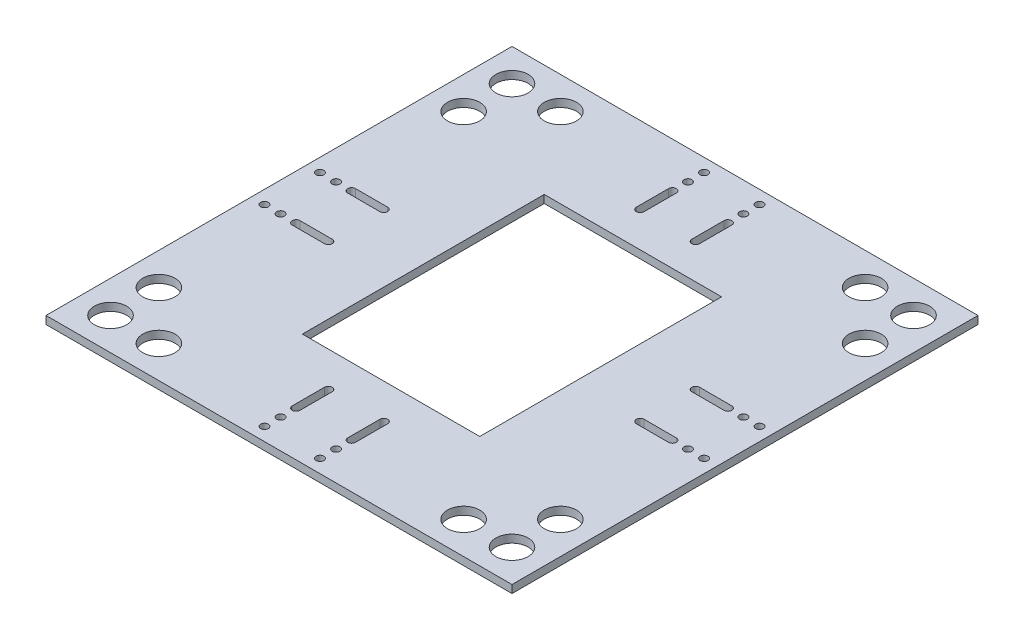
SolidWorks part; units mm, degrees
material "Acrylic (Medium-high impact)"
ref_plane "Front Plane" through (0, 0, 0) normal (0, 0, 1) x (1, 0, 0)
ref_plane "Top Plane" through (0, 0, 0) normal (0, 1, 0) x (1, 0, 0)
ref_plane "Right Plane" through (0, 0, 0) normal (1, 0, 0) x (0, 0, -1)
sketch "Sketch3" plane through (0, 0, 0) normal (0, 1, 0) x (1, 0, 0)
  line L1 (0, 0) -> (183.52, 0)
  line L2 (0, 0) -> (0, 183.52)
  line L3 (0, 183.52) -> (183.52, 183.52)
  line L4 (183.52, 0) -> (183.52, 183.52)
  dimension "D1" = 183.52
  dimension "D2" = 183.52
extrude "Boss-Extrude1" add sketch "Sketch3" along normal blind 3.0988
sketch "Sketch4" plane through (0, 3.0988, 0) normal (0, 1, 0) x (1, 0, 0)
  line L0 (0, 91.76) -> (183.52, 91.76) construction
  line L1 (0, 183.52) -> (0, 0) construction
  line L2 (183.52, 0) -> (183.52, 183.52) construction
  line L3 (91.76, 183.52) -> (91.76, 0) construction
  line L4 (-1025.7031, 102.682) -> (48974.2969, 102.682) construction
  line L5 (17.646, 101.158) -> (30.346, 101.158)
  line L6 (17.646, 104.206) -> (30.346, 104.206)
  line L7 (183.52, 183.52) -> (0, 183.52) construction
  line L8 (0, 0) -> (183.52, 0) construction
  line L9 (-1025.7031, 80.838) -> (48974.2969, 80.838) construction
  line L10 (17.646, 79.314) -> (30.346, 79.314)
  line L11 (17.646, 82.362) -> (30.346, 82.362)
  line L12 (1240.6011, 80.838) -> (-48759.3989, 80.838) construction
  line L13 (1209.2232, 102.682) -> (-48790.7768, 102.682) construction
  line L14 (165.874, 82.362) -> (153.174, 82.362)
  line L15 (165.874, 79.314) -> (153.174, 79.314)
  line L16 (165.874, 104.206) -> (153.174, 104.206)
  line L17 (165.874, 101.158) -> (153.174, 101.158)
  line L18 (80.838, -759.6953) -> (80.838, 49240.3047) construction
  line L19 (79.314, 153.167) -> (79.314, 165.867)
  line L20 (82.362, 153.167) -> (82.362, 165.867)
  line L21 (102.682, -759.6953) -> (102.682, 49240.3047) construction
  line L22 (101.158, 153.167) -> (101.158, 165.867)
  line L23 (104.206, 153.167) -> (104.206, 165.867)
  line L24 (104.206, 30.353) -> (104.206, 17.653)
  line L25 (101.158, 30.353) -> (101.158, 17.653)
  line L26 (82.362, 30.353) -> (82.362, 17.653)
  line L27 (79.314, 30.353) -> (79.314, 17.653)
  circle A0 centre (5.2, 102.682) radius 1.524
  arc A1 (17.646, 104.206) -> (17.646, 101.158) centre (17.646, 102.682) ccw
  circle A2 centre (11.55, 102.682) radius 1.524
  arc A3 (30.346, 101.158) -> (30.346, 104.206) centre (30.346, 102.682) ccw
  arc A4 (30.346, 82.362) -> (30.346, 79.314) centre (30.346, 80.838) cw
  circle A5 centre (11.55, 80.838) radius 1.524
  arc A6 (17.646, 79.314) -> (17.646, 82.362) centre (17.646, 80.838) cw
  circle A7 centre (5.2, 80.838) radius 1.524
  circle A8 centre (178.32, 80.838) radius 1.524
  arc A9 (165.874, 79.314) -> (165.874, 82.362) centre (165.874, 80.838) ccw
  circle A10 centre (171.97, 80.838) radius 1.524
  arc A11 (153.174, 82.362) -> (153.174, 79.314) centre (153.174, 80.838) ccw
  arc A12 (153.174, 101.158) -> (153.174, 104.206) centre (153.174, 102.682) cw
  circle A13 centre (171.97, 102.682) radius 1.524
  arc A14 (165.874, 104.206) -> (165.874, 101.158) centre (165.874, 102.682) cw
  circle A15 centre (178.32, 102.682) radius 1.524
  circle A16 centre (80.838, 178.313) radius 1.524
  circle A17 centre (80.838, 171.963) radius 1.524
  arc A18 (82.362, 165.867) -> (79.314, 165.867) centre (80.838, 165.867) ccw
  arc A19 (79.314, 153.167) -> (82.362, 153.167) centre (80.838, 153.167) ccw
  arc A20 (104.206, 153.167) -> (101.158, 153.167) centre (102.682, 153.167) cw
  arc A21 (101.158, 165.867) -> (104.206, 165.867) centre (102.682, 165.867) cw
  circle A22 centre (102.682, 171.963) radius 1.524
  circle A23 centre (102.682, 178.313) radius 1.524
  circle A24 centre (102.682, 5.207) radius 1.524
  circle A25 centre (102.682, 11.557) radius 1.524
  arc A26 (101.158, 17.653) -> (104.206, 17.653) centre (102.682, 17.653) ccw
  arc A27 (104.206, 30.353) -> (101.158, 30.353) centre (102.682, 30.353) ccw
  arc A28 (79.314, 30.353) -> (82.362, 30.353) centre (80.838, 30.353) cw
  arc A29 (82.362, 17.653) -> (79.314, 17.653) centre (80.838, 17.653) cw
  circle A30 centre (80.838, 11.557) radius 1.524
  circle A31 centre (80.838, 5.207) radius 1.524
  dimension "D1" = 3.048
  dimension "D2" = 6.35
  dimension "D3" = 6.096
  dimension "D4" = 12.7
  dimension "D9" = 6.096
  dimension "D10" = 5.207
  dimension "D11" = 12.7
  dimension "D12" = 79.314
  dimension "D7" = 3.048
  dimension "D5" = 5.2
  dimension "D6" = 79.314
  dimension "D8" = 6.35
extrude "Cut-Extrude1" cut sketch "Sketch4" against normal through all
sketch "Sketch5" plane through (0, 3.0988, 0) normal (0, 1, 0) x (1, 0, 0)
  line L0 (0, 91.76) -> (183.52, 91.76) construction
  line L1 (56.835, 139.385) -> (126.685, 139.385)
  line L2 (56.835, 139.385) -> (56.835, 44.135)
  line L3 (56.835, 44.135) -> (126.685, 44.135)
  line L4 (126.685, 139.385) -> (126.685, 44.135)
  line L5 (183.52, 183.52) -> (0, 183.52) construction
  line L6 (0, 183.52) -> (0, 0) construction
  line L7 (183.52, 0) -> (183.52, 183.52) construction
  line L9 (0, 0) -> (183.52, 0) construction
  line L13 (91.76, 183.52) -> (91.76, 0) construction
  circle A0 centre (170.82, 151.77) radius 6.35
  circle A1 centre (170.82, 170.82) radius 6.35
  circle A2 centre (151.77, 170.82) radius 6.35
  circle A3 centre (170.82, 31.75) radius 6.35
  circle A4 centre (12.7, 31.75) radius 6.35
  circle A5 centre (12.7, 12.7) radius 6.35
  circle A6 centre (31.75, 12.7) radius 6.35
  circle A7 centre (151.77, 12.7) radius 6.35
  circle A8 centre (31.75, 170.82) radius 6.35
  circle A9 centre (12.7, 170.82) radius 6.35
  circle A10 centre (12.7, 151.77) radius 6.35
  circle A11 centre (170.82, 12.7) radius 6.35
  point P12 (56.835, 91.76)
  point P26 (91.76, 139.385)
  dimension "D5" = 12.7
  dimension "D6" = 12.7
  dimension "D7" = 12.7
  dimension "D3" = 12.7
  dimension "D1" = 69.85
  dimension "D2" = 95.25
  dimension "D4" = 12.7
  dimension "D8" = 31.75
  dimension "D9" = 31.75
extrude "Cut-Extrude2" cut sketch "Sketch5" against normal up to next
